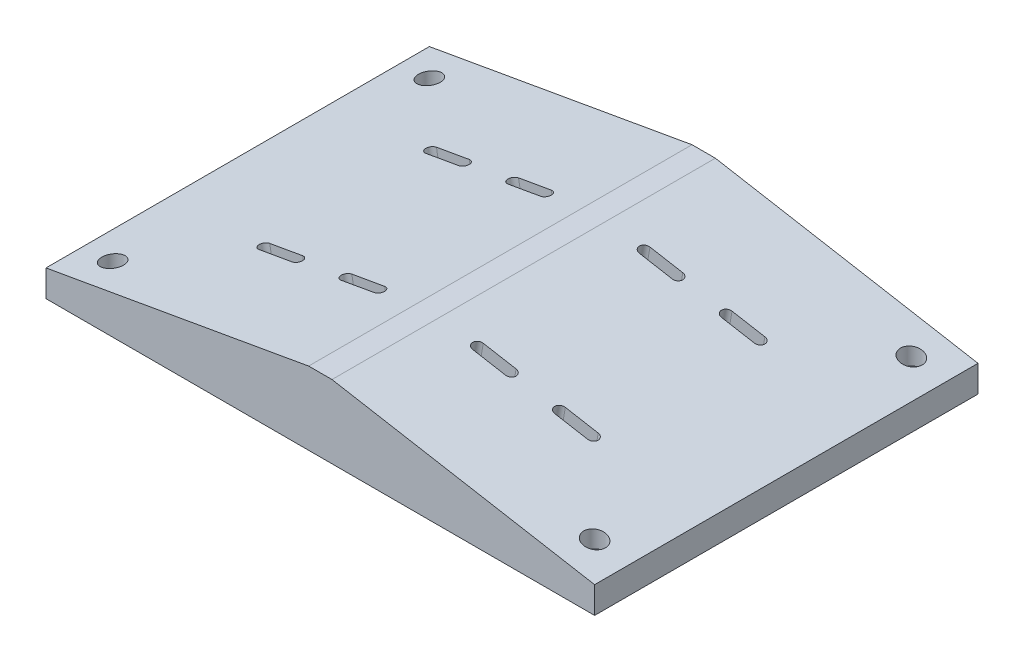
SolidWorks part; units mm, degrees
ref_plane "Front Plane" through (0, 0, 0) normal (0, 0, 1) x (1, 0, 0)
ref_plane "Top Plane" through (0, 0, 0) normal (0, 1, 0) x (1, 0, 0)
ref_plane "Right Plane" through (0, 0, 0) normal (1, 0, 0) x (0, 0, -1)
sketch "Sketch1" plane through (0, 0, 0) normal (0, 0, 1) x (1, 0, 0)
  line L0 (-82.2846, 0) -> (82.2846, 0)
  line L1 (-82.2846, 0) -> (-82.2846, 8)
  line L2 (-82.2846, 8) -> (-3.5, 21.8919)
  line L4 (82.2846, 8) -> (82.2846, 0)
  line L5 (-82.2846, 8) -> (82.2846, 8) construction
  line L6 (-3.5, 21.8919) -> (3.5, 21.8919)
  line L7 (3.5, 21.8919) -> (82.2846, 8)
  line L8 (0, 0) -> (0, 88.6136) construction
  point P4 (0, 0)
  dimension "D1" = 10
  dimension "D2" = 80
  dimension "D3" = 8
  dimension "D4" = 7
extrude "Boss-Extrude1" add sketch "Sketch1" along normal mid plane 115 contours L2 L6 L7 L4 L0 L1
sketch "Sketch2" plane through (-3.8493, 21.8303, 0) normal (-0.1736, 0.9848, 0) x (0.9848, 0.1736, 0)
  line L0 (-41.1108, -25) -> (-16.1108, -25)
  line L5 (-11.1108, -25) -> (-21.1108, -25) construction
  line L8 (-46.1108, 25) -> (-36.1108, 25) construction
  line L27 (-46.1108, 26.6) -> (-36.1108, 26.6)
  line L28 (-46.1108, 23.4) -> (-36.1108, 23.4)
  line L29 (-79.6453, 0) -> (82.4237, 0) construction
  line L32 (-41.1108, 25) -> (-16.1108, 25)
  line L35 (-41.1108, 25) -> (-41.1108, -25)
  line L38 (-41.1108, -25) -> (-16.1108, -25)
  line L39 (-16.1108, 25) -> (-16.1108, -25)
  line L40 (-41.1108, 25) -> (-16.1108, -25) construction
  line L41 (-41.1108, -25) -> (-16.1108, 25) construction
  line L42 (-11.1108, -26.6) -> (-21.1108, -26.6)
  line L43 (82.4237, -57.5) -> (82.4237, 57.5) construction
  line L44 (-79.6453, -57.5) -> (-79.6453, 57.5) construction
  line L45 (-28.6108, 9.8455) -> (-28.6108, -9.8455) construction
  line L46 (-11.1108, 25) -> (-21.1108, 25) construction
  line L47 (-11.1108, 26.6) -> (-21.1108, 26.6)
  line L48 (-11.1108, 23.4) -> (-21.1108, 23.4)
  line L49 (-11.1108, -23.4) -> (-21.1108, -23.4)
  line L50 (-46.1108, -25) -> (-36.1108, -25) construction
  line L51 (-46.1108, -26.6) -> (-36.1108, -26.6)
  line L52 (-46.1108, -23.4) -> (-36.1108, -23.4)
  arc A0 (-46.1108, 26.6) -> (-46.1108, 23.4) centre (-46.1108, 25) ccw
  arc A1 (-36.1108, 23.4) -> (-36.1108, 26.6) centre (-36.1108, 25) ccw
  arc A8 (-11.1108, 26.6) -> (-11.1108, 23.4) centre (-11.1108, 25) cw
  arc A9 (-21.1108, 23.4) -> (-21.1108, 26.6) centre (-21.1108, 25) cw
  arc A10 (-11.1108, -26.6) -> (-11.1108, -23.4) centre (-11.1108, -25) ccw
  arc A11 (-21.1108, -23.4) -> (-21.1108, -26.6) centre (-21.1108, -25) ccw
  arc A12 (-46.1108, -26.6) -> (-46.1108, -23.4) centre (-46.1108, -25) cw
  arc A13 (-36.1108, -23.4) -> (-36.1108, -26.6) centre (-36.1108, -25) cw
  point P3 (1.3892, 0)
  point P15 (-28.6108, 0)
  point P18 (-28.6108, 0)
  point P22 (-41.1108, 25)
  point P32 (-16.1108, 25)
  point P37 (-16.1108, -25)
  point P44 (-41.1108, -25)
  dimension "D1" = 50
  dimension "D2" = 25
  dimension "D3" = 3.2
  dimension "D4" = 30
  dimension "D5" = 10
extrude "Cut-Extrude1" cut sketch "Sketch2" against normal blind 7 contours L28 A1 L27 A0 | L28 A1 L32 L35 | A9 L32 L39 L48 A8 L47 | A9 L48 L39 L32 | L49 A11 L38 L39 | L38 A11 L42 A10 L49 L39 | A13 L52 L35 L0 | A13 L0 L35 L52 A12 L51
sketch "Sketch7" plane through (-3.8493, 21.8303, 0) normal (-0.1736, 0.9848, 0) x (0.9848, 0.1736, 0)
  line L0 (-47.7108, 25) -> (-34.5108, 25) construction
  line L1 (-28.6108, 9.0393) -> (-28.6108, -12.0611) construction
  line L2 (-39.4509, 22.125) -> (-37.7911, 25) construction
  line L3 (-37.7911, 25) -> (-39.4509, 27.875) construction
  line L4 (-39.4509, 27.875) -> (-42.7707, 27.875) construction
  line L5 (-42.7707, 27.875) -> (-44.4306, 25) construction
  line L6 (-44.4306, 25) -> (-42.7707, 22.125) construction
  line L7 (-42.7707, 22.125) -> (-39.4509, 22.125) construction
  line L8 (-46.1108, 23.4) -> (-36.1108, 23.4) construction
  line L9 (-49.8608, 25) -> (-32.3608, 25) construction
  line L10 (-49.8608, 27.875) -> (-32.3608, 27.875)
  line L11 (-49.8608, 22.125) -> (-32.3608, 22.125)
  line L12 (-41.1108, 25) -> (-16.1108, 25) construction
  line L13 (-29.8621, 0) -> (-14.5177, 0) construction
  line L14 (-41.1108, 25) -> (-41.1108, -25) construction
  line L15 (-49.8608, -25) -> (-32.3608, -25) construction
  line L16 (-49.8608, -27.875) -> (-32.3608, -27.875)
  line L25 (-49.8608, -22.125) -> (-32.3608, -22.125)
  line L26 (-42.7707, -22.125) -> (-39.4509, -22.125) construction
  line L29 (-44.4306, -25) -> (-42.7707, -22.125) construction
  line L32 (-42.7707, -27.875) -> (-44.4306, -25) construction
  line L45 (-39.4509, -27.875) -> (-42.7707, -27.875) construction
  line L46 (-41.1108, -25) -> (-16.1108, -25) construction
  line L47 (-16.1108, 25) -> (-16.1108, -25) construction
  line L48 (-41.1108, 25) -> (-16.1108, -25) construction
  line L49 (-41.1108, -25) -> (-16.1108, 25) construction
  line L50 (-37.7911, -25) -> (-39.4509, -27.875) construction
  line L51 (-39.4509, -22.125) -> (-37.7911, -25) construction
  line L52 (-47.7108, -25) -> (-34.5108, -25) construction
  line L53 (-7.3608, 25) -> (-24.8608, 25) construction
  line L54 (-7.3608, 27.875) -> (-24.8608, 27.875)
  line L55 (-7.3608, 22.125) -> (-24.8608, 22.125)
  line L56 (-7.3608, -25) -> (-24.8608, -25) construction
  line L57 (-7.3608, -27.875) -> (-24.8608, -27.875)
  line L58 (-7.3608, -22.125) -> (-24.8608, -22.125)
  line L59 (-9.5108, -25) -> (-22.7108, -25) construction
  line L60 (-17.7707, -22.125) -> (-19.4306, -25) construction
  line L61 (-19.4306, -25) -> (-17.7707, -27.875) construction
  line L62 (-17.7707, -27.875) -> (-14.4509, -27.875) construction
  line L63 (-14.4509, -27.875) -> (-12.7911, -25) construction
  line L64 (-12.7911, -25) -> (-14.4509, -22.125) construction
  line L65 (-14.4509, -22.125) -> (-17.7707, -22.125) construction
  line L66 (-16.1108, 25) -> (-16.1108, -25) construction
  line L67 (-14.4509, 22.125) -> (-17.7707, 22.125) construction
  line L68 (-12.7911, 25) -> (-14.4509, 22.125) construction
  line L69 (-14.4509, 27.875) -> (-12.7911, 25) construction
  line L70 (-17.7707, 27.875) -> (-14.4509, 27.875) construction
  line L71 (-19.4306, 25) -> (-17.7707, 27.875) construction
  line L72 (-17.7707, 22.125) -> (-19.4306, 25) construction
  line L73 (-9.5108, 25) -> (-22.7108, 25) construction
  arc A0 (-46.1108, 26.6) -> (-46.1108, 23.4) centre (-46.1108, 25) ccw construction
  arc A1 (-36.1108, 23.4) -> (-36.1108, 26.6) centre (-36.1108, 25) ccw construction
  circle A2 centre (-41.1108, 25) radius 2.875 construction
  arc A3 (-49.8608, 27.875) -> (-49.8608, 22.125) centre (-49.8608, 25) ccw
  arc A4 (-32.3608, 22.125) -> (-32.3608, 27.875) centre (-32.3608, 25) ccw
  arc A5 (-49.8608, -27.875) -> (-49.8608, -22.125) centre (-49.8608, -25) cw
  arc A6 (-32.3608, -22.125) -> (-32.3608, -27.875) centre (-32.3608, -25) cw
  circle A7 centre (-41.1108, -25) radius 2.875 construction
  arc A8 (-7.3608, 27.875) -> (-7.3608, 22.125) centre (-7.3608, 25) cw
  arc A9 (-24.8608, 22.125) -> (-24.8608, 27.875) centre (-24.8608, 25) cw
  arc A10 (-7.3608, -27.875) -> (-7.3608, -22.125) centre (-7.3608, -25) ccw
  arc A11 (-24.8608, -22.125) -> (-24.8608, -27.875) centre (-24.8608, -25) ccw
  circle A12 centre (-16.1108, -25) radius 2.875 construction
  circle A13 centre (-16.1108, 25) radius 2.875 construction
  point P20 (-41.1108, 25)
  point P33 (-41.1108, -25)
  point P50 (-16.1108, 25)
  point P57 (-16.1108, -25)
  point P81 (-28.6108, 0)
  line M5 (-36.1108, 23.4) -> (-46.1108, 23.4)
  arc M6 (-46.1108, 23.4) -> (-46.1108, 26.6) centre (-46.1108, 25) cw
  line M7 (-46.1108, 26.6) -> (-36.1108, 26.6)
  arc M8 (-36.1108, 26.6) -> (-36.1108, 23.4) centre (-36.1108, 25) cw
  line M59 (-21.1108, -23.4) -> (-11.1108, -23.4)
  arc M60 (-11.1108, -23.4) -> (-11.1108, -26.6) centre (-11.1108, -25) cw
  line M61 (-11.1108, -26.6) -> (-21.1108, -26.6)
  arc M62 (-21.1108, -26.6) -> (-21.1108, -23.4) centre (-21.1108, -25) cw
  line M63 (-11.1108, 23.4) -> (-21.1108, 23.4)
  arc M64 (-21.1108, 23.4) -> (-21.1108, 26.6) centre (-21.1108, 25) cw
  line M65 (-21.1108, 26.6) -> (-11.1108, 26.6)
  arc M66 (-11.1108, 26.6) -> (-11.1108, 23.4) centre (-11.1108, 25) cw
  line M67 (-46.1108, -23.4) -> (-36.1108, -23.4)
  arc M68 (-36.1108, -23.4) -> (-36.1108, -26.6) centre (-36.1108, -25) cw
  line M69 (-36.1108, -26.6) -> (-46.1108, -26.6)
  arc M70 (-46.1108, -26.6) -> (-46.1108, -23.4) centre (-46.1108, -25) cw
  dimension "D1" = 5.75
  dimension "D2" = 17.5
  dimension "D3" = 25
  dimension "D4" = 50
extrude "Cut-Extrude4" cut sketch "Sketch7" against normal through all from surface contours L11 A4 L12 L14 M8 M5 | L12 A4 L10 A3 L11 L14 M5 M6 M7 M8 | L12 L14 M5 M8 | L14 L12 M8 M7 M6 M5 | A9 L55 A8 L54 M66 M63 M64 M65 | M63 M66 M65 M64 | A6 L25 A5 L16 M70 M67 M68 M69 | M67 M70 M69 M68 | L58 A11 L57 A10 M62 M59 M60 M61 | M59 M62 M61 M60 region at (-44.3355, 14.6915, -27.6355) region at (-55.548, 12.7144, 25) region at (-8.5028, 21.0097, -25) region at (-19.7153, 19.0327, 27.6355) region at (-44.3355, 14.6915, -25) region at (-19.7153, 19.0327, 25) region at (-19.7153, 19.0327, -25) region at (-44.3355, 14.6915, 25) starting at face at (-43.12, 7.7978, 25)
mirror "Mirror1" about plane through (0, 0, 0) normal (1, 0, 0) of "Cut-Extrude1", "Cut-Extrude4"
ref_plane "Plane1" through (0, 8, 0) normal (0, -1, 0) x (-1, 0, 0)
sketch "Sketch8" plane through (0, 8, 0) normal (0, -1, 0) x (-1, 0, 0)
  line L0 (-82.2846, -57.5) -> (-82.2846, 57.5) construction
  line L1 (-72.2846, -47.5) -> (72.2846, -47.5) construction
  line L2 (-72.2846, -47.5) -> (-72.2846, 47.5) construction
  line L3 (-72.2846, 47.5) -> (72.2846, 47.5) construction
  line L4 (72.2846, -47.5) -> (72.2846, 47.5) construction
  line L5 (-72.2846, -47.5) -> (72.2846, 47.5) construction
  line L6 (-72.2846, 47.5) -> (72.2846, -47.5) construction
  line L8 (82.2846, -57.5) -> (3.5, -57.5) construction
  point P0 (0, 0)
  dimension "D1" = 10
  dimension "D2" = 10
hole_wizard "CBORE for M3 SHCS1" positions "Sketch13" profile "Sketch12" counterbore size "M3" standard "ANSI Metric" end condition through all
sketch "Sketch13" plane through (0, 8, 0) normal (0, -1, 0) x (-1, 0, 0)
  point P0 (-72.2846, 47.5)
  point P3 (-72.2846, -47.5)
  point P6 (72.2846, 47.5)
  point P9 (72.2846, -47.5)
sketch "Sketch12" plane through (72.2846, 8, -47.5) normal (1, 0, 0) x (0, 0, 1)
  line L0 (0, 0) -> (0, 8)
  line L1 (0, 8) -> (1.8, 8)
  line L3 (1.8, 8) -> (1.8, 3)
  line L4 (1.8, 3) -> (3.25, 3)
  line L5 (3.25, 3) -> (3.25, 0)
  line L7 (3.25, 0) -> (0, 0)
  line L11 (0, -6.35) -> (0, 107.95) construction
  dimension "Thru Hole Dia." = 3.6
  dimension "Thru Hole Depth" = 8
  dimension "C'Bore Dia." = 6.5
  dimension "C'Bore Depth" = 3
sketch "Sketch14" plane through (0, 5, 0) normal (0, 1, 0) x (1, 0, 0)
  circle A0 centre (-72.2846, -47.5) radius 3.25 construction
  circle A1 centre (-72.2846, 47.5) radius 3.25 construction
  circle A2 centre (-72.2846, -47.5) radius 3.25
  circle A3 centre (-72.2846, 47.5) radius 3.25
  circle A4 centre (72.2846, -47.5) radius 3.25 construction
  circle A5 centre (72.2846, 47.5) radius 3.25 construction
  circle A6 centre (72.2846, -47.5) radius 3.25
  circle A7 centre (72.2846, 47.5) radius 3.25
extrude "Cut-Extrude5" cut sketch "Sketch14" along normal through all
